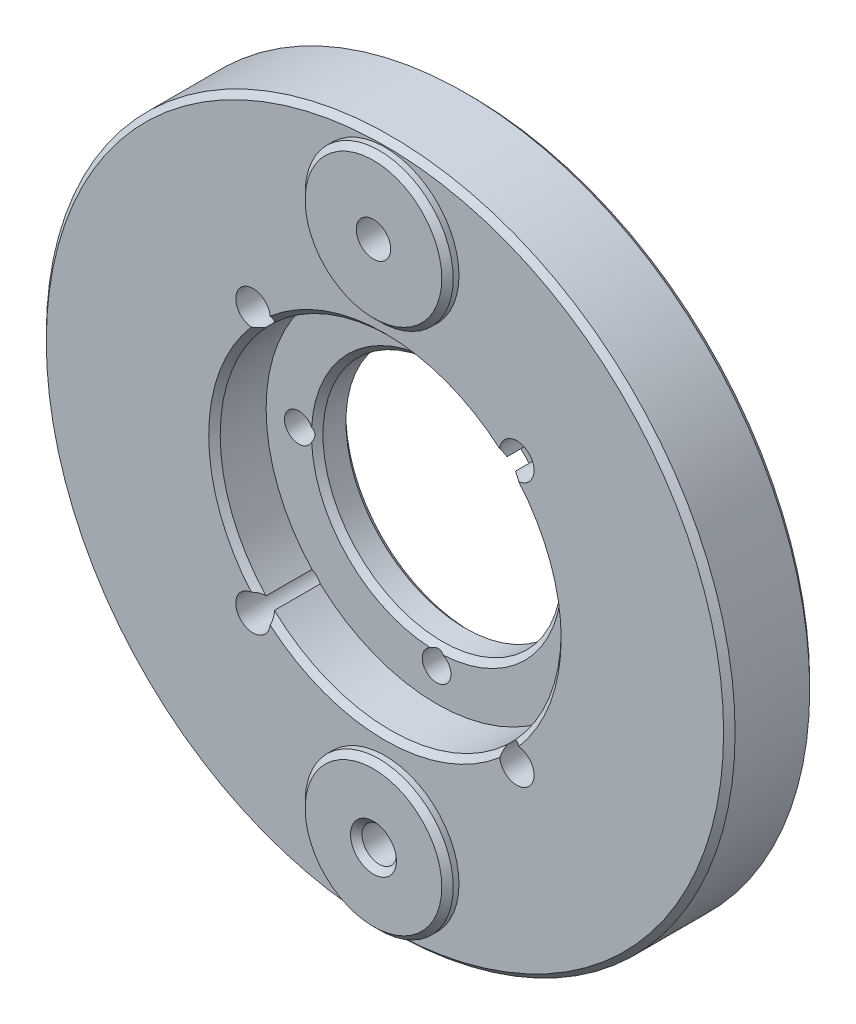
SolidWorks part; units mm, degrees
note: '?' marks a value the reader was unsure of. The reader was unsure of these and kept them because the rebuilt part matched: shared geometry of "Sketch5<2>".
ref_plane "Front Plane" through (0, 0, 0) normal (0, 0, 1) x (1, 0, 0)
ref_plane "Top Plane" through (0, 0, 0) normal (0, 1, 0) x (1, 0, 0)
ref_plane "Right Plane" through (0, 0, 0) normal (1, 0, 0) x (0, 0, -1)
sketch "Sketch1" plane through (0, 0, 0) normal (0, 0, 1) x (1, 0, 0)
  circle A0 centre (0, 0) radius 20.8
  circle A1 centre (0, 0) radius 29.7
  dimension "D1" = 41.6
  dimension "D2" = 59.4
extrude "Boss-Extrude1" add sketch "Sketch1" along normal blind 6
sketch "Sketch2" plane through (0, 0, 0) normal (0, 0, 1) x (1, 0, 0)
  line L0 (0, 24) -> (0, 0) construction
  line L1 (0, 20.8) -> (0, 29.7) construction
  circle A0 centre (0, 24) radius 2.5
  circle A1 centre (0, 0) radius 20.8 construction
  circle A2 centre (0, 0) radius 29.7 construction
  circle A3 centre (24, 0) radius 2.5
  circle A4 centre (0, -24) radius 2.5
  circle A5 centre (-24, 0) radius 2.5
  point P20 (0, 0)
  dimension "D1" = 5
  dimension "D3" = 48
  dimension "D2" = 4
sketch "Sketch3" plane through (0, 0, 0) normal (0, 0, 1) x (1, 0, 0)
  circle A0 centre (0, 0) radius 60
  circle A1 centre (0, 0) radius 29.7
  circle A2 centre (0, 0) radius 29.7
  dimension "D2" = 120
  dimension "D1" = 0
extrude "Boss-Extrude2" add sketch "Sketch3" along normal offset from surface (15 mm away) 9 up to face at (29.7, 0, 6) offset beyond the face yes
sketch "Sketch4" plane through (0, 0, 0) normal (0, 0, 1) x (1, 0, 0)
  line L0 (-22.981, 22.981) -> (0, 0) construction
  line L1 (0, 24) -> (0, 0) construction
  circle A0 centre (-22.981, 22.981) radius 3
  circle A1 centre (22.981, 22.981) radius 3
  circle A2 centre (22.981, -22.981) radius 3
  circle A3 centre (-22.981, -22.981) radius 3
  point P16 (0, 0)
  dimension "D3" = 6
  dimension "D1" = 45
  dimension "D4" = 65
  dimension "D2" = 4
extrude "Cut-Extrude1" cut sketch "Sketch4" along normal through all both and the other way through all
extrude "Cut-Extrude3" cut sketch "Sketch2" along normal through all both
ref_axis "Axis1" through (0, 0, -0.5) along (0, 0, 1)?
ref_plane "Plane1" through (0, 0, 0) normal (-0.4226, 0.9063, 0) x (0, 0, 1)
sketch "Sketch5" plane through (0, 0, 15) normal (0, 0, 1) x (1, 0, 0)
  line L0 (0, 33) -> (0, -33) construction
  line L1 (0, 58.8) -> (0, -58.8) construction
  circle A0 centre (0, 45.9) radius 12.9
  circle A1 centre (0, -45.9) radius 12.9
  circle A2 centre (0, 45.9) radius 3
  circle A3 centre (0, -45.9) radius 3
  point P6 (0, 0)
  point P15 (0, 0)
  dimension "D2" = 25.8
  dimension "D6" = 6
  dimension "D3" = 117.6
  dimension "D4" = 66
  dimension "D1" = 2
  dimension "D5" = 2
extrude "Boss-Extrude3" add sketch "Sketch5" along normal blind 2
extrude "Cut-Extrude4" cut sketch "Sketch5<2>" against normal through all both and the other way through all contours A3 | A2
sketch "Sketch5<2>" plane through (0, 0, 15) normal (0, 0, 1) x (1, 0, 0) same geometry as "Sketch5"
chamfer "Chamfer1" distance 1 angle 45 11 edges at (60, 0, 0) (60, 0, 15) (0, -29.7, 15) (-29.7, 0, 15) (0, 29.7, 15) (29.7, 0, 15) (20.8, 0, 6) (20.8, 0, 0) (3, -45.9, 17) (12.9, -45.9, 17) (12.9, 45.9, 17)
other "Intersect1"
